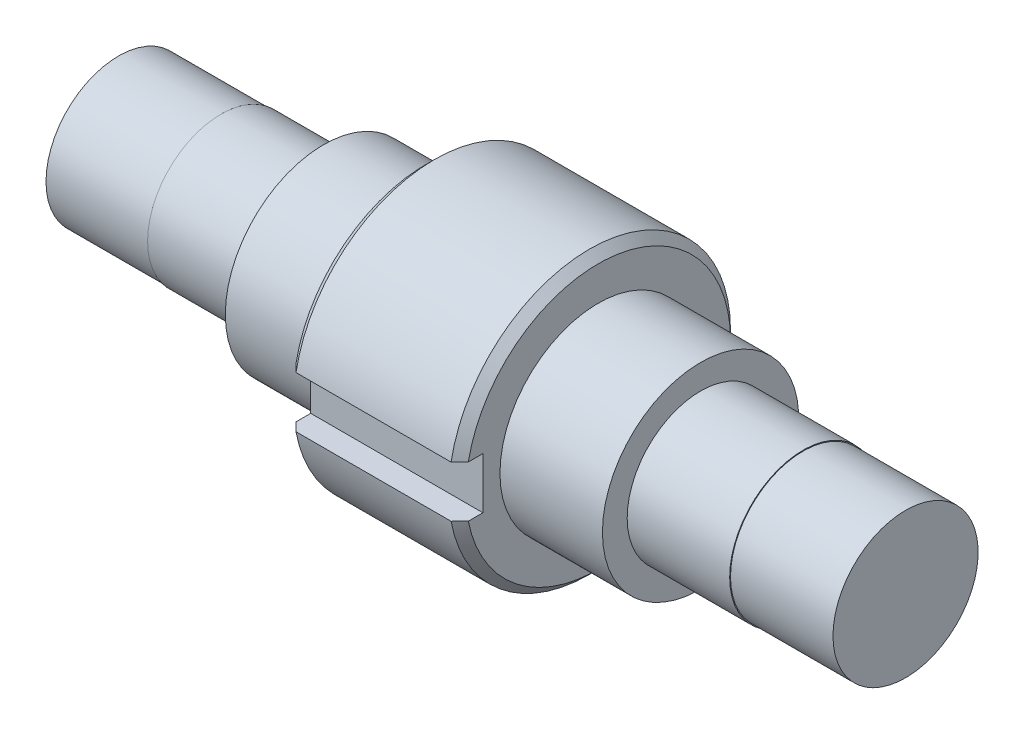
SolidWorks part; units mm, degrees
material "Plain Carbon Steel"
ref_plane "Front Plane" through (0, 0, 0) normal (0, 0, 1) x (1, 0, 0)
ref_plane "Top Plane" through (0, 0, 0) normal (0, 1, 0) x (1, 0, 0)
ref_plane "Right Plane" through (0, 0, 0) normal (1, 0, 0) x (0, 0, -1)
sketch "Sketch1" plane through (0, 0, 0) normal (0, 0, 1) x (1, 0, 0)
  line L0 (-39.3673, 0) -> (-85.4486, 0) construction
  line L1 (-39.3673, 0) -> (-39.3673, 16.5) construction
  line L2 (-29.2861, 16.5) -> (-49.4486, 16.5)
  line L3 (-49.4486, 16.5) -> (-49.4486, 11.5)
  line L4 (-49.4486, 11.5) -> (-61.4486, 11.5)
  line L5 (-61.4486, 11.5) -> (-61.4486, 8.5) construction
  line L6 (-61.4486, 8.5) -> (-85.4486, 8.5) construction
  line L7 (-85.4486, 8.5) -> (-85.4486, 0)
  line L8 (-29.2861, 16.5) -> (-29.2861, 11.5)
  line L9 (-29.2861, 11.5) -> (-17.2861, 11.5)
  line L10 (-17.2861, 11.5) -> (-17.2861, 8.5) construction
  line L11 (-17.2861, 8.5) -> (6.7139, 8.5) construction
  line L12 (6.7139, 8.5) -> (6.7139, 0)
  line L13 (-85.4486, 0) -> (6.7139, 0)
  line L14 (-49.4486, -11.5) -> (-49.4486, 11.5) construction
  line L15 (-61.4486, 8.6) -> (-73.4486, 8.6)
  line L16 (-73.4486, 8.6) -> (-73.4486, 8.5)
  line L17 (-73.4486, 8.5) -> (-85.4486, 8.5)
  line L18 (-61.4486, 11.5) -> (-61.4486, 8.6)
  line L19 (-5.2861, 8.5) -> (6.7139, 8.5)
  line L20 (-5.2861, 8.6) -> (-5.2861, 8.5)
  line L21 (-17.2861, 8.6) -> (-5.2861, 8.6)
  line L22 (-17.2861, 11.5) -> (-17.2861, 8.6)
  line L23 (-49.4486, -11.5) -> (-49.4486, 11.5) construction
  point P11 (-39.3673, 16.5)
  point P18 (-49.4486, 16.5)
  dimension "D1" = 12
  dimension "D2" = 36
  dimension "D3" = 8.5
  dimension "D4" = 8.6
  dimension "D5" = 12
revolve "Revolve1" add sketch "Sketch1" angle 360 about L13
sketch "Sketch3" plane through (-29.2861, 0, 0) normal (1, 0, 0) x (0, 0, -1)
  line L0 (0, 0) -> (-16.5, 0) construction
  line L1 (-16.225, -3) -> (-13.5, -3)
  line L2 (-16.225, 3) -> (-13.5, 3)
  line L3 (-13.5, -3) -> (-13.5, 3)
  circle A0 centre (0, 0) radius 16.5 construction
  arc A1 (-16.225, 3) -> (-16.225, -3) centre (0, 0) ccw
  dimension "D1" = 3
  dimension "D2" = 6
extrude "Cut-Extrude1" cut sketch "Sketch3" against normal through all
chamfer "Chamfer1" distance 1 angle 45 2 edges at (-49.4486, 0, -16.5) (-29.2861, 0, -16.5)
